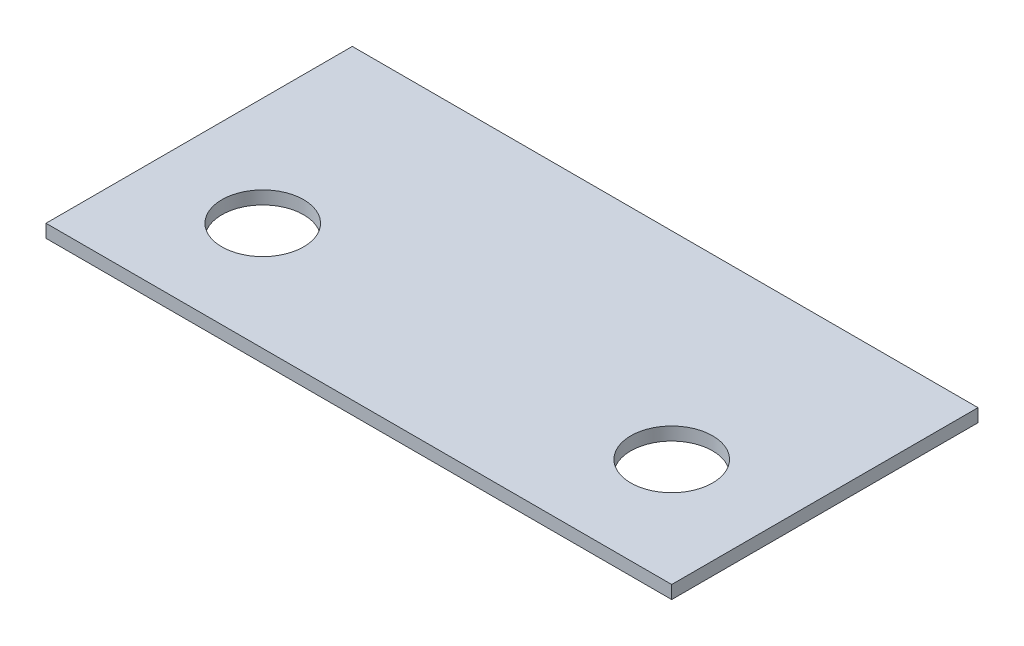
SolidWorks part; units mm, degrees
ref_plane "Front Plane" through (0, 0, 0) normal (0, 0, 1) x (1, 0, 0)
ref_plane "Top Plane" through (0, 0, 0) normal (0, 1, 0) x (1, 0, 0)
ref_plane "Right Plane" through (0, 0, 0) normal (1, 0, 0) x (0, 0, -1)
sketch "Sketch1" plane through (0, 0, 0) normal (0, 1, 0) x (1, 0, 0)
  line L1 (-382.5, 187.25) -> (382.5, 187.25)
  line L2 (-382.5, 187.25) -> (-382.5, -187.25)
  line L3 (-382.5, -187.25) -> (382.5, -187.25)
  line L4 (382.5, 187.25) -> (382.5, -187.25)
  line L5 (-382.5, 187.25) -> (382.5, -187.25) construction
  line L6 (-382.5, -187.25) -> (382.5, 187.25) construction
  point P0 (0, 0)
  dimension "D1" = 374.5
  dimension "D2" = 765
extrude "Boss-Extrude1" add sketch "Sketch1" along normal blind 16
sketch "Sketch2" plane through (0, 16, 0) normal (0, 1, 0) x (1, 0, 0)
  line L0 (-382.5, -54.75) -> (382.5, -54.75) construction
  line L2 (382.5, -187.25) -> (382.5, 187.25) construction
  line L3 (0, -187.25) -> (0, 187.25) construction
  line L4 (-382.5, -187.25) -> (382.5, -187.25) construction
  line L5 (382.5, 187.25) -> (-382.5, 187.25) construction
  line L6 (-382.5, 195.25) -> (382.5, 195.25) construction
  line L7 (-382.5, -187.25) -> (382.5, -187.25)
  line L8 (-382.5, -187.25) -> (-382.5, 577.75)
  line L9 (-382.5, 577.75) -> (382.5, 577.75)
  line L10 (382.5, -187.25) -> (382.5, 577.75)
  circle A0 centre (-250, -54.75) radius 50
  circle A1 centre (250, -54.75) radius 50
  point P2 (0, 0)
  point P3 (0, 0)
  dimension "D1" = 100
  dimension "D2" = 500
  dimension "D3" = 500
extrude "Cut-Extrude1" cut sketch "Sketch2" against normal up to next and the other way through all contours A0 | A1 region at (-250, 16, 54.75) region at (250, 16, 54.75)
